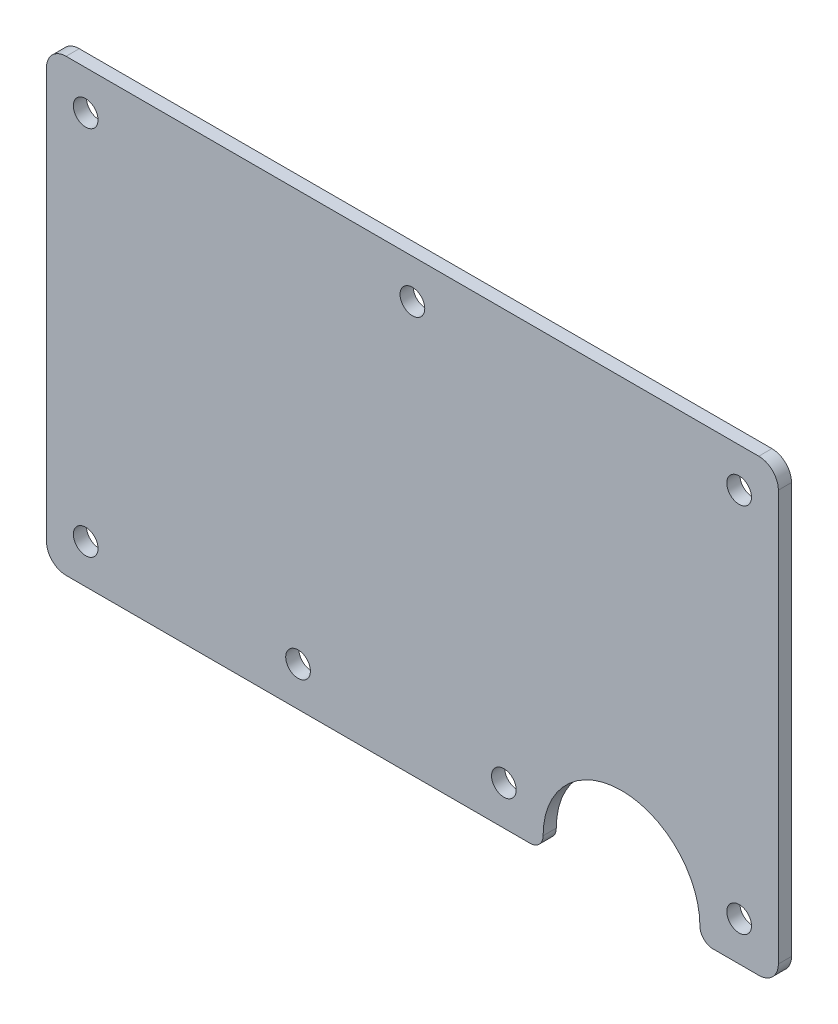
SolidWorks part; units mm, degrees
ref_plane "Front Plane" through (0, 0, 0) normal (0, 0, 1) x (1, 0, 0)
ref_plane "Top Plane" through (0, 0, 0) normal (0, 1, 0) x (1, 0, 0)
ref_plane "Right Plane" through (0, 0, 0) normal (1, 0, 0) x (0, 0, -1)
ref_plane "Plane1" through (0, 0, 1.6) normal (0, 0, 1) x (1, 0, 0)
sketch "Sketch1" plane through (0, 0, 1.6) normal (0, 0, 1) x (1, 0, 0)
  line L0 (0, 53.3207) -> (0, 3.4732)
  line L1 (2.3813, 1.092) -> (58.7375, 1.092)
  line L2 (80.9625, 1.092) -> (86.5187, 1.092)
  line L3 (88.9, 3.4732) -> (88.9, 53.3207)
  line L4 (86.5187, 55.702) -> (2.3813, 55.702)
  line L5 (79.375, -1.3322) -> (79.375, -50001.3322) construction
  line L6 (2.3813, 1.092) -> (58.7375, 1.092) construction
  line L7 (30.5594, 1.092) -> (30.5594, 11.6574) construction
  line L8 (44.45, 55.702) -> (44.45, 38.5848) construction
  circle A0 centre (4.7625, 50.9395) radius 1.5
  circle A1 centre (4.7625, 5.8545) radius 1.5
  circle A2 centre (84.1375, 5.8545) radius 1.5
  circle A3 centre (84.1375, 50.9395) radius 1.5
  circle A4 centre (30.5594, 5.8545) radius 1.5
  circle A5 centre (55.5625, 5.8545) radius 1.5
  circle A6 centre (44.45, 50.9395) radius 1.5
  arc A7 (0, 3.4732) -> (2.3813, 1.092) centre (2.3813, 3.4732) ccw
  arc A8 (58.7375, 1.092) -> (60.325, 2.6795) centre (58.7375, 2.6795) ccw
  arc A9 (60.325, 2.6795) -> (79.375, 2.6795) centre (69.85, 2.6795) cw
  arc A10 (79.375, 2.6795) -> (80.9625, 1.092) centre (80.9625, 2.6795) ccw
  arc A11 (86.5187, 1.092) -> (88.9, 3.4732) centre (86.5187, 3.4732) ccw
  arc A12 (88.9, 53.3207) -> (86.5187, 55.702) centre (86.5187, 53.3207) ccw
  arc A13 (2.3813, 55.702) -> (0, 53.3207) centre (2.3813, 53.3207) ccw
  point P33 (30.5594, 1.092)
  point P36 (0, 0)
  point P37 (44.45, 55.702)
  dimension "D3" = 9.525
  dimension "D4" = 3
  dimension "D5" = 1.5875
  dimension "D14" = 2.3813
  dimension "D1" = 88.9
  dimension "D2" = 54.61
  dimension "D6" = 4.7625
  dimension "D7" = 4.7625
  dimension "D8" = 19.05
  dimension "D9" = 4.7625
  dimension "D10" = 4.7625
  dimension "D11" = 4.7625
  dimension "D12" = 4.7625
  dimension "D13" = 3.175
  dimension "D15" = 4.7625
  dimension "D16" = 4.7625
  dimension "D17" = 4.7625
  dimension "D18" = 4.7625
  dimension "D19" = 4.7625
extrude "Boss-Extrude1" add sketch "Sketch1" against normal blind 1.6
